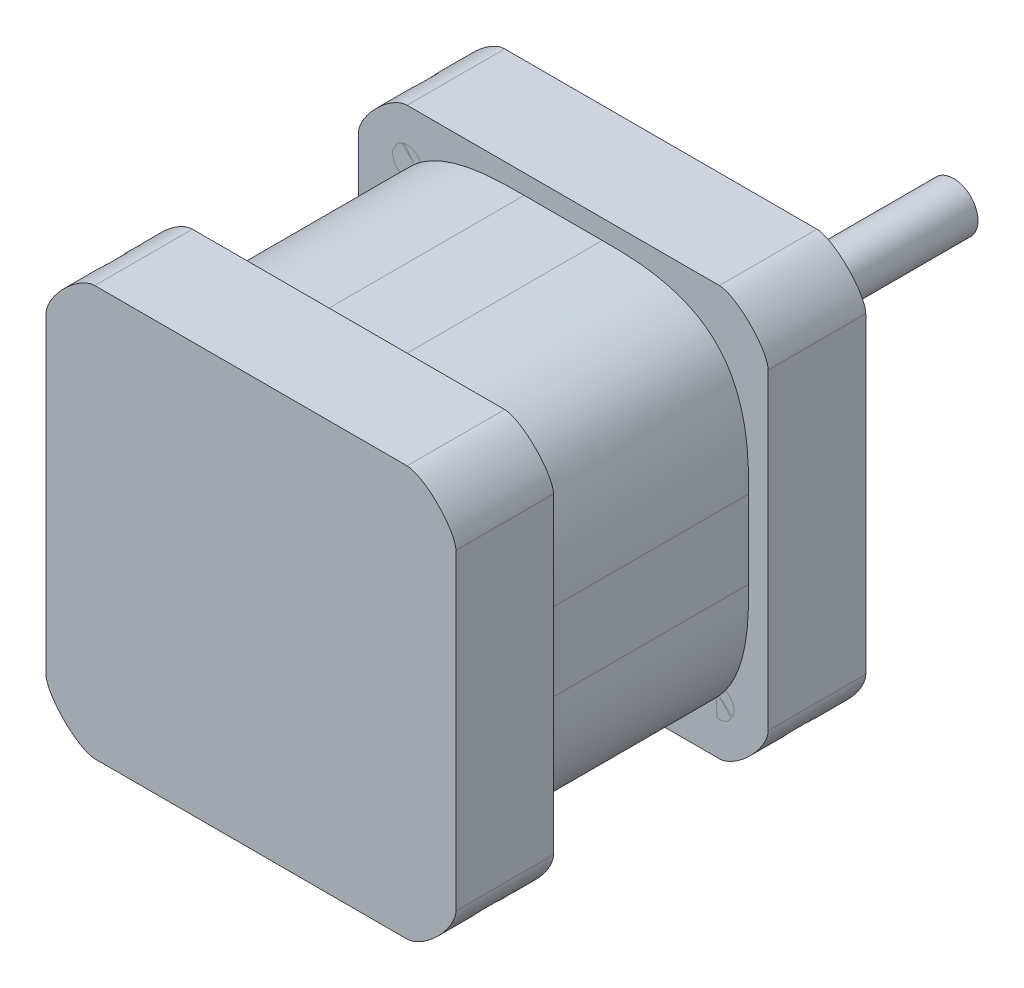
SolidWorks part; units mm, degrees
ref_plane "Front Plane" through (0, 0, 0) normal (0, 0, 1) x (1, 0, 0)
ref_plane "Top Plane" through (0, 0, 0) normal (0, 1, 0) x (1, 0, 0)
ref_plane "Right Plane" through (0, 0, 0) normal (1, 0, 0) x (0, 0, -1)
sketch "Sketch1" plane through (0, 0, 0) normal (0, 0, 1) x (1, 0, 0)
  line L1 (-19, 19) -> (19, 19)
  line L2 (-19, 19) -> (-19, -19)
  line L3 (-19, -19) -> (19, -19)
  line L4 (19, 19) -> (19, -19)
  line L5 (-19, 19) -> (19, -19) construction
  line L6 (-19, -19) -> (19, 19) construction
  point P0 (0, 0)
  dimension "D1" = 38
  dimension "D2" = 38
extrude "Boss-Extrude1" add sketch "Sketch1" along normal blind 22 from offset 10
sketch "Sketch2" plane through (0, 0, 0) normal (0, 0, 1) x (1, 0, 0)
  line L1 (-21, 21) -> (21, 21)
  line L2 (-21, 21) -> (-21, -21)
  line L3 (-21, -21) -> (21, -21)
  line L4 (21, 21) -> (21, -21)
  line L5 (-21, 21) -> (21, -21) construction
  line L6 (-21, -21) -> (21, 21) construction
  point P0 (0, 0)
extrude "Boss-Extrude2" add sketch "Sketch2" along normal blind 10 contours L1 L4 L3 L2
sketch "Sketch4" plane through (0, 0, 0) normal (0, 0, 1) x (1, 0, 0)
  line L1 (-21, 21) -> (21, 21)
  line L2 (-21, 21) -> (-21, -21)
  line L3 (-21, -21) -> (21, -21)
  line L4 (21, 21) -> (21, -21)
  line L5 (-21, 21) -> (21, -21) construction
  line L6 (-21, -21) -> (21, 21) construction
  point P0 (0, 0)
extrude "Boss-Extrude3" add sketch "Sketch4" along normal blind 10 from offset 32
fillet "Fillet1" radius 15 4 edges at (-19, 19, 21) (-19, -19, 21) (19, -19, 21) (19, 19, 21) curvature continuous yes
fillet "Fillet2" radius 5 8 edges at (-21, -21, 37) (-21, -21, 5) (21, -21, 5) (21, -21, 37) (21, 21, 5) (-21, 21, 5) (-21, 21, 37) (21, 21, 37) conic radius 10
sketch "Sketch5" plane through (0, 0, 0) normal (0, 0, 1) x (1, 0, 0)
  circle A0 centre (0, 0) radius 2.5
extrude "Boss-Extrude4" add sketch "Sketch5" against normal blind 30
sketch "Sketch6" plane through (0, 0, 0) normal (0, 0, 1) x (1, 0, 0)
  line L0 (21, 16) -> (21, -16) construction
  line L1 (-16, 21) -> (16, 21) construction
  line L2 (-16, -21) -> (16, -21) construction
  line L3 (-21, 16) -> (-21, -16) construction
  line L4 (-16, -21) -> (16, -21) construction
  circle A0 centre (16, 16) radius 1.5
  circle A1 centre (-16, 16) radius 1.485
  circle A2 centre (16, -16) radius 1.5
  circle A3 centre (-16, -16) radius 1.485
  point P10 (0, -21)
  dimension "D3" = 5
  dimension "D4" = 5
  dimension "D5" = 3
  dimension "D6" = 3
  dimension "D1" = 5
  dimension "D2" = 5
  dimension "D7" = 21
extrude "Boss-Extrude5" add sketch "Sketch6" along normal up to surface (10 mm away) from surface separate body up to face at (-4, 4, 10) starting at face at (2.5, 0, 0)
extrude "Cut-Extrude1" cut sketch "Sketch6<2>" along normal blind 9
sketch "Sketch6<2>" plane through (0, 0, 0) normal (0, 0, 1) x (1, 0, 0) same geometry as "Sketch6"
sketch "Sketch3" plane through (0, 0, 0) normal (0, 0, 1) x (1, 0, 0)
